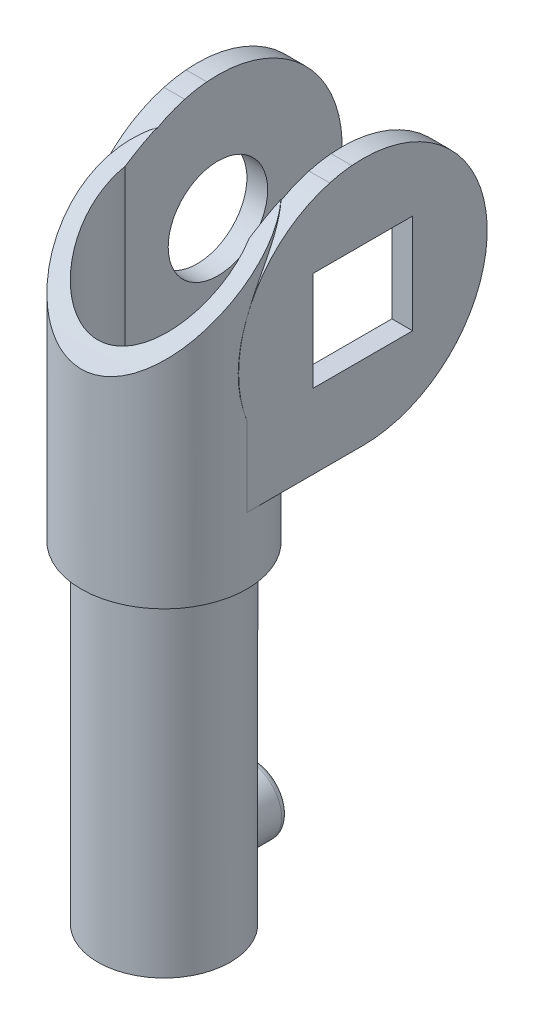
SolidWorks part; units mm, degrees
material "Copper"
ref_plane "Front Plane" through (0, 0, 0) normal (0, 0, 1) x (1, 0, 0)
ref_plane "Top Plane" through (0, 0, 0) normal (0, 1, 0) x (1, 0, 0)
ref_plane "Right Plane" through (0, 0, 0) normal (1, 0, 0) x (0, 0, -1)
sketch "Sketch1" plane through (0, 0, 0) normal (0, 1, 0) x (1, 0, 0)
  circle A0 centre (0, 0) radius 3
  circle A1 centre (0, 0) radius 5
  dimension "D1" = 6
  dimension "D2" = 10
extrude "Boss-Extrude1" add sketch "Sketch1" along normal blind 3
sketch "Sketch2" plane through (0, 3, 0) normal (0, 1, 0) x (1, 0, 0)
  circle A0 centre (0, 0) radius 4
  circle A1 centre (0, 0) radius 5
extrude "Boss-Extrude2" add sketch "Sketch2" along normal blind 16
ref_plane "Plane1" through (5, 0, 0) normal (1, 0, 0) x (0, 0, -1)
sketch "Sketch3" plane through (5, 0, 0) normal (1, 0, 0) x (0, 0, -1)
  line L0 (7, 4) -> (0, 4)
  line L2 (0, 4) -> (0, 8.8074)
  arc A1 (7, 4) -> (0, 8.8074) centre (7, 11.5) ccw
extrude "Boss-Extrude3" add sketch "Sketch3" against normal blind 10
sketch "Sketch4" plane through (5, 0, 0) normal (1, 0, 0) x (0, 0, -1)
  line L0 (-5, 19) -> (-5, 0) construction
  line L1 (-5, 11.5) -> (-9.7286, 16.2286)
  line L2 (-9.7286, 16.2286) -> (-5.4428, 22.642)
  line L3 (-5.4428, 22.642) -> (7, 19)
  arc A1 (7, 4) -> (0, 14.1926) centre (7, 11.5) ccw construction
  spline S0 degree 3 poles (7, 19) (6.3181, 19) (1.658, 18.3512) (-3.3607, 13.1999) (-5, 11.5) knots 0 0 0 0 0.141151 1 1 1 1
extrude "Cut-Extrude1" cut sketch "Sketch4" against normal blind 16
sketch "Sketch5" plane through (0, 3, 0) normal (0, 1, 0) x (1, 0, 0)
  circle A0 centre (0, 0) radius 4
extrude "Cut-Extrude2" cut sketch "Sketch5" along normal blind 18
sketch "Sketch7" plane through (0, 3, 0) normal (0, 1, 0) x (1, 0, 0)
  line L0 (0, 0) -> (-3.75, 0)
  line L1 (0, 0) -> (3.75, 0)
  line L2 (3.75, 0) -> (3.75, 16.1606)
  line L3 (3.75, 16.1606) -> (-3.75, 16.1606)
  line L4 (-3.75, 16.1606) -> (-3.75, 0)
extrude "Cut-Extrude3" cut sketch "Sketch7" along normal blind 30
sketch "Sketch8" plane through (5, 0, 0) normal (1, 0, 0) x (0, 0, -1)
  line L1 (4, 14.5) -> (10, 14.5)
  line L2 (4, 14.5) -> (4, 8.5)
  line L3 (4, 8.5) -> (10, 8.5)
  line L4 (10, 14.5) -> (10, 8.5)
  line L5 (4, 14.5) -> (10, 8.5) construction
  line L6 (4, 8.5) -> (10, 14.5) construction
  point P0 (7, 11.5)
extrude "Cut-Extrude4" cut sketch "Sketch8" against normal blind 7
sketch "Sketch9" plane through (-5, 0, 0) normal (-1, 0, 0) x (0, 0, 1)
  circle A0 centre (-7, 11.5) radius 3
extrude "Cut-Extrude5" cut sketch "Sketch9" against normal blind 7
sketch "Sketch10" plane through (0, 0, 0) normal (0, -1, 0) x (1, 0, 0)
  circle A0 centre (0, 0) radius 4
  circle A2 centre (0, 0) radius 3
extrude "Boss-Extrude4" add sketch "Sketch10" along normal blind 20
ref_plane "Plane2" through (0, 0, -4) normal (0, 0, 1) x (1, 0, 0)
sketch "Sketch11" plane through (0, 0, -4) normal (0, 0, 1) x (1, 0, 0)
  circle A0 centre (0, -16) radius 2
extrude "Boss-Extrude5" add sketch "Sketch11" along normal up to surface and the other way blind 1.5 up to face at (0, -20, -4)
fillet "Fillet1" radius 0.4 1 edges at (2, -16, -5.5)
